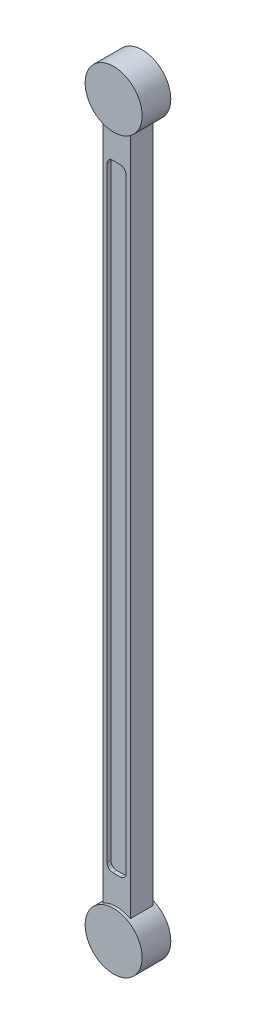
SolidWorks part; units mm, degrees
ref_plane "Front" through (0, 0, 0) normal (0, 0, 1) x (1, 0, 0)
ref_plane "Top" through (0, 0, 0) normal (0, 1, 0) x (1, 0, 0)
ref_plane "Right" through (0, 0, 0) normal (1, 0, 0) x (0, 0, -1)
sketch "Sketch1" plane through (-505.7052, -1154.2469, 0) normal (0, 0, 1) x (1, 0, 0)
  line L0 (486.1052, 2330.8055) -> (486.1052, 1197.687)
  line L1 (482.7052, 1195.9866) -> (482.7052, 2332.5059)
  line L2 (525.3052, 1197.687) -> (525.3052, 2330.8055)
  line L3 (528.7052, 2332.5059) -> (528.7052, 1195.9866)
  line L4 (486.2052, 1258.2462) -> (486.2052, 2330.7605)
  line L5 (489.7052, 2329.3546) -> (489.7052, 1258.2462)
  line L6 (499.7052, 2326.9677) -> (499.7052, 1258.2462)
  line L7 (511.7052, 1258.2462) -> (511.7052, 2326.9677)
  line L8 (521.7052, 1258.2462) -> (521.7052, 2329.3546)
  line L9 (525.2052, 2330.7605) -> (525.2052, 1258.2462)
  line L10 (486.2052, 1258.2462) -> (489.7052, 1258.2462)
  line L11 (525.2052, 1258.2462) -> (521.7052, 1258.2462)
  line L12 (511.7052, 1244.7462) -> (511.7052, 1248.2462)
  line L13 (499.7052, 1244.7462) -> (499.7052, 1248.2462)
  line L14 (511.7052, 1258.2462) -> (521.7052, 1258.2462)
  line L15 (499.7052, 1258.2462) -> (499.7052, 1248.2462)
  line L16 (511.7052, 1258.2462) -> (511.7052, 1248.2462)
  line L17 (499.7052, 1258.2462) -> (489.7052, 1258.2462)
  line L18 (499.7052, 1258.2462) -> (511.7052, 1258.2462)
  line L19 (511.7052, 1244.7462) -> (499.7052, 1244.7462)
  line L20 (499.7052, 1248.2462) -> (511.7052, 1248.2462)
  line L21 (499.7052, 2280.2462) -> (499.7052, 2283.7462)
  line L22 (489.7052, 2270.2462) -> (486.2052, 2270.2462)
  line L23 (511.7052, 2280.2462) -> (511.7052, 2283.7462)
  line L24 (521.7052, 2270.2462) -> (525.2052, 2270.2462)
  line L25 (521.7052, 2270.2462) -> (511.7052, 2270.2462)
  line L26 (511.7052, 2280.2462) -> (511.7052, 2270.2462)
  line L27 (499.7052, 2280.2462) -> (499.7052, 2270.2462)
  line L28 (489.7052, 2270.2462) -> (499.7052, 2270.2462)
  line L29 (499.7052, 2270.2462) -> (499.7052, 2244.371)
  line L30 (511.7052, 2270.2462) -> (499.7052, 2270.2462)
  line L31 (511.7052, 2257.0727) -> (511.7052, 2270.2462)
  line L32 (528.7052, 2277.7072) -> (528.7052, 2264.4354)
  line L33 (525.3052, 2264.9247) -> (525.3052, 2280.0122)
  line L34 (482.7052, 2234.556) -> (482.7052, 2308.8932)
  line L35 (486.1052, 2306.5882) -> (486.1052, 2236.519)
  line L36 (499.7052, 2283.7462) -> (511.7052, 2283.7462)
  line L37 (525.2052, 2270.2462) -> (525.2052, 2264.8669)
  line L38 (486.2052, 2236.5768) -> (486.2052, 2270.2462)
  line L39 (511.7052, 2280.2462) -> (499.7052, 2280.2462)
  line L40 (489.7052, 2270.2462) -> (489.7052, 2238.5975)
  line L41 (521.7052, 2262.8462) -> (521.7052, 2270.2462)
  line L42 (526.8021, 2265.7889) -> (527.2334, 2266.0379)
  line L43 (534.0206, 2434.9688) -> (531.9075, 2430.4373)
  circle A0 centre (505.7052, 1154.2462) radius 17.5
  circle A1 centre (505.7052, 1154.2462) radius 47.6577
  arc A2 (511.7052, 1244.7462) -> (525.2052, 1258.2462) centre (511.7052, 1258.2462) ccw
  arc A3 (486.2052, 1258.2462) -> (499.7052, 1244.7462) centre (499.7052, 1258.2462) ccw
  arc A4 (511.7052, 1248.2462) -> (521.7052, 1258.2462) centre (511.7052, 1258.2462) ccw
  arc A5 (489.7052, 1258.2462) -> (499.7052, 1248.2462) centre (499.7052, 1258.2462) ccw
  circle A6 centre (505.7052, 1154.2462) radius 22.5
  circle A7 centre (505.7052, 1154.2462) radius 27.5
  circle A8 centre (505.7052, 1154.2462) radius 16.5
  circle A9 centre (505.7052, 2374.2462) radius 47.6577
  circle A10 centre (505.7052, 2374.2462) radius 27.5
  circle A11 centre (505.7052, 2374.2462) radius 22.5
  arc A12 (499.7052, 2283.7462) -> (486.2052, 2270.2462) centre (499.7052, 2270.2462) ccw
  arc A13 (525.2052, 2270.2462) -> (511.7052, 2283.7462) centre (511.7052, 2270.2462) ccw
  arc A14 (521.7052, 2270.2462) -> (511.7052, 2280.2462) centre (511.7052, 2270.2462) ccw
  arc A15 (499.7052, 2280.2462) -> (489.7052, 2270.2462) centre (499.7052, 2270.2462) ccw
  circle A16 centre (505.7052, 2374.2462) radius 17.5
  circle A17 centre (505.7052, 2374.2462) radius 16.5
sketch "Sketch2" plane through (-505.7052, 0, 2556.1257) normal (0, 1, 0) x (1, 0, 0)
  line L0 (505.7052, 2532.1257) -> (505.7052, 2556.1257) construction
  line L1 (501.0475, 2580.6257) -> (549.0475, 2580.6257)
  line L2 (501.0475, 2580.6257) -> (501.0475, 2580.1257)
  line L3 (549.0475, 2580.1257) -> (549.0475, 2580.6257)
  line L4 (458.0475, 2575.1257) -> (458.0475, 2537.1257)
  line L5 (551.2498, 2580.1257) -> (463.0475, 2580.1257)
  line L6 (551.2498, 2532.1257) -> (551.434, 2532.1447)
  line L7 (551.434, 2532.1447) -> (551.6167, 2532.2017)
  line L8 (551.6167, 2532.2017) -> (551.7967, 2532.2961)
  line L9 (551.7967, 2532.2961) -> (551.9725, 2532.4272)
  line L10 (551.9725, 2532.4272) -> (552.1428, 2532.5942)
  line L11 (552.1428, 2532.5942) -> (552.3064, 2532.7956)
  line L12 (552.3064, 2532.7956) -> (552.4618, 2533.0299)
  line L13 (552.4618, 2533.0299) -> (552.6081, 2533.2955)
  line L14 (552.6081, 2533.2955) -> (552.744, 2533.5902)
  line L15 (552.744, 2533.5902) -> (552.8685, 2533.9118)
  line L16 (552.8685, 2533.9118) -> (552.9808, 2534.2578)
  line L17 (552.9808, 2534.2578) -> (553.0798, 2534.6257)
  line L18 (553.0798, 2534.6257) -> (553.1649, 2535.0126)
  line L19 (553.1649, 2535.0126) -> (553.2355, 2535.4156)
  line L20 (553.2355, 2535.4156) -> (553.2909, 2535.8316)
  line L21 (553.2909, 2535.8316) -> (553.3308, 2536.2575)
  line L22 (553.3308, 2536.2575) -> (553.3549, 2536.6899)
  line L23 (553.3549, 2536.6899) -> (553.3629, 2537.1257)
  line L24 (551.2498, 2532.1257) -> (463.0475, 2532.1257)
  line L25 (553.3629, 2575.1257) -> (458.0475, 2575.1257)
  line L26 (553.3629, 2575.1257) -> (553.3549, 2575.5615)
  line L27 (553.3549, 2575.5615) -> (553.3308, 2575.9939)
  line L28 (553.3308, 2575.9939) -> (553.2909, 2576.4198)
  line L29 (553.2909, 2576.4198) -> (553.2355, 2576.8358)
  line L30 (553.2355, 2576.8358) -> (553.1649, 2577.2388)
  line L31 (553.1649, 2577.2388) -> (553.0798, 2577.6257)
  line L32 (553.0798, 2577.6257) -> (552.9808, 2577.9936)
  line L33 (552.9808, 2577.9936) -> (552.8685, 2578.3396)
  line L34 (552.8685, 2578.3396) -> (552.744, 2578.6612)
  line L35 (552.744, 2578.6612) -> (552.6081, 2578.9559)
  line L36 (552.6081, 2578.9559) -> (552.4618, 2579.2215)
  line L37 (552.4618, 2579.2215) -> (552.3064, 2579.4558)
  line L38 (552.3064, 2579.4558) -> (552.1428, 2579.6572)
  line L39 (552.1428, 2579.6572) -> (551.9725, 2579.8242)
  line L40 (551.9725, 2579.8242) -> (551.7967, 2579.9553)
  line L41 (551.7967, 2579.9553) -> (551.6167, 2580.0497)
  line L42 (551.6167, 2580.0497) -> (551.434, 2580.1067)
  line L43 (551.434, 2580.1067) -> (551.2498, 2580.1257)
  line L44 (553.3629, 2537.1257) -> (553.3629, 2575.1257)
  line L45 (458.0475, 2537.1257) -> (553.3629, 2537.1257)
  line L46 (522.3697, 2530.8597) -> (522.8128, 2531.7094)
  line L47 (538.4272, 2528.1257) -> (522.8128, 2531.7094)
  line L48 (486.0475, 2524.2368) -> (486.4833, 2524.2516)
  line L49 (486.4833, 2524.2516) -> (486.9157, 2524.2959)
  line L50 (486.9157, 2524.2959) -> (487.3416, 2524.3693)
  line L51 (487.3416, 2524.3693) -> (487.7576, 2524.4713)
  line L52 (487.7576, 2524.4713) -> (488.1606, 2524.6012)
  line L53 (488.1606, 2524.6012) -> (488.5475, 2524.7578)
  line L54 (488.5475, 2524.7578) -> (488.9154, 2524.9401)
  line L55 (488.9154, 2524.9401) -> (489.2614, 2525.1466)
  line L56 (489.2614, 2525.1466) -> (489.583, 2525.3758)
  line L57 (489.583, 2525.3758) -> (489.8777, 2525.626)
  line L58 (489.8777, 2525.626) -> (490.1432, 2525.8951)
  line L59 (490.1432, 2525.8951) -> (490.3776, 2526.1813)
  line L60 (490.3776, 2526.1813) -> (490.579, 2526.4822)
  line L61 (490.579, 2526.4822) -> (490.7459, 2526.7956)
  line L62 (490.7459, 2526.7956) -> (490.8771, 2527.1192)
  line L63 (490.8771, 2527.1192) -> (490.9715, 2527.4504)
  line L64 (490.9715, 2527.4504) -> (491.0284, 2527.7868)
  line L65 (491.0284, 2527.7868) -> (491.0475, 2528.1257)
  line L66 (527.6129, 2528.1257) -> (496.0475, 2528.1257)
  line L67 (496.0475, 2528.1257) -> (491.0475, 2528.1257)
  line L68 (522.8128, 2531.7094) -> (522.552, 2532.1257)
  line L69 (538.4272, 2532.1257) -> (538.4272, 2528.1257)
  line L70 (496.0475, 2528.1257) -> (496.0475, 2532.1257)
  line L71 (458.0475, 2556.1257) -> (553.3629, 2556.1257) construction
  line L72 (505.7052, 2575.1257) -> (505.7052, 2700.0052) construction
  arc A0 (501.0475, 2580.6257) -> (502.984, 2581.1257) centre (501.0475, 2584.6257) ccw
  arc A1 (547.111, 2581.1257) -> (549.0475, 2580.6257) centre (549.0475, 2584.6257) ccw
  arc A2 (463.0475, 2580.1257) -> (458.0475, 2575.1257) centre (463.0475, 2575.1257) ccw
  arc A3 (458.0475, 2537.1257) -> (463.0475, 2532.1257) centre (463.0475, 2537.1257) ccw
  arc A4 (491.6106, 2532.2989) -> (486.0475, 2524.2368) centre (495.5173, 2523.6527) ccw
  arc A5 (522.3697, 2530.8597) -> (519.3677, 2532.1257) centre (513.1227, 2513.1257) ccw
  arc A6 (522.8128, 2531.7094) -> (520.3216, 2532.3493) centre (513.0839, 2499.0025) ccw
sketch "Sketch3" plane through (0, 0, 0) normal (0, 0, 1) x (1, 0, 0)
  line L0 (23, 1178.259) -> (23, 41.7397)
  line L2 (-23, 1178.259) -> (-23, 41.7397)
  arc A0 (-23, 41.7397) -> (23, 41.7397) centre (0, 0) ccw
  arc A1 (23, 1178.259) -> (-23, 1178.259) centre (0, 1219.9994) ccw
extrude "Extrude1" add sketch "Sketch3" against normal up to vertex (19 mm away) and the other way blind 19.05 up to point (-47.6577, 0, -19)
sketch "Sketch4" plane through (0, 0, 19.05) normal (0, 0, 1) x (1, 0, 0)
  line L0 (-6, 93.9994) -> (6, 93.9994) construction
  line L1 (6, 1125.9994) -> (-6, 1125.9994) construction
  line L5 (15.888, 1178.259) -> (15.888, 41.7397)
  line L6 (15.888, 1116.3474) -> (15.888, 103.6514)
  line L7 (-6.236, 1125.9994) -> (6.236, 1125.9994)
  line L8 (-15.888, 41.7397) -> (-15.888, 1178.259)
  line L9 (-15.888, 103.6514) -> (-15.888, 1116.3474)
  line L10 (-6.236, 93.9994) -> (6.236, 93.9994)
  arc A0 (6.236, 93.9994) -> (15.888, 103.6514) centre (6.236, 103.6514) ccw
  arc A1 (-6.236, 93.9994) -> (-15.888, 103.6514) centre (-6.236, 103.6514) cw
  arc A2 (6.236, 1125.9994) -> (15.888, 1116.3474) centre (6.236, 1116.3474) cw
  arc A3 (-6.236, 1125.9994) -> (-15.888, 1116.3474) centre (-6.236, 1116.3474) ccw
  dimension "D3" = 9.652
  dimension "D1" = 7.112
  dimension "D2" = 7.112
extrude "Cut-Extrude1" cut sketch "Sketch4" against normal blind 6.35
sketch "Sketch5" plane through (0, 0, -19) normal (0, 0, -1) x (-1, 0, 0)
  line L4 (-15.888, 1116.3474) -> (-15.888, 103.6514)
  line L5 (6.236, 1125.9994) -> (-6.236, 1125.9994)
  line L6 (15.888, 103.6514) -> (15.888, 1116.3474)
  line L7 (-6.236, 93.9994) -> (6.236, 93.9994)
  line L8 (-15.888, 1116.3474) -> (-15.888, 103.6514)
  line L9 (6.236, 1125.9994) -> (-6.236, 1125.9994)
  line L10 (15.888, 103.6514) -> (15.888, 1116.3474)
  line L11 (-6.236, 93.9994) -> (6.236, 93.9994)
  arc A4 (-15.888, 103.6514) -> (-6.236, 93.9994) centre (-6.236, 103.6514) ccw
  arc A5 (-6.236, 1125.9994) -> (-15.888, 1116.3474) centre (-6.236, 1116.3474) ccw
  arc A6 (15.888, 1116.3474) -> (6.236, 1125.9994) centre (6.236, 1116.3474) ccw
  arc A7 (6.236, 93.9994) -> (15.888, 103.6514) centre (6.236, 103.6514) ccw
  arc A8 (-15.888, 103.6514) -> (-6.236, 93.9994) centre (-6.236, 103.6514) ccw
  arc A9 (-6.236, 1125.9994) -> (-15.888, 1116.3474) centre (-6.236, 1116.3474) ccw
  arc A10 (15.888, 1116.3474) -> (6.236, 1125.9994) centre (6.236, 1116.3474) ccw
  arc A11 (6.236, 93.9994) -> (15.888, 103.6514) centre (6.236, 103.6514) ccw
  dimension "D1" = 0
extrude "Cut-Extrude2" cut sketch "Sketch5" against normal blind 6.35
sketch "Sketch6" plane through (0, 0, 19.05) normal (0, 0, 1) x (1, 0, 0)
  circle A0 centre (0, 1219.9994) radius 47.6577
  circle A1 centre (0, 0) radius 47.6572
extrude "Extrude2" add sketch "Sketch6" along normal blind 4.826 and the other way blind 43.18
